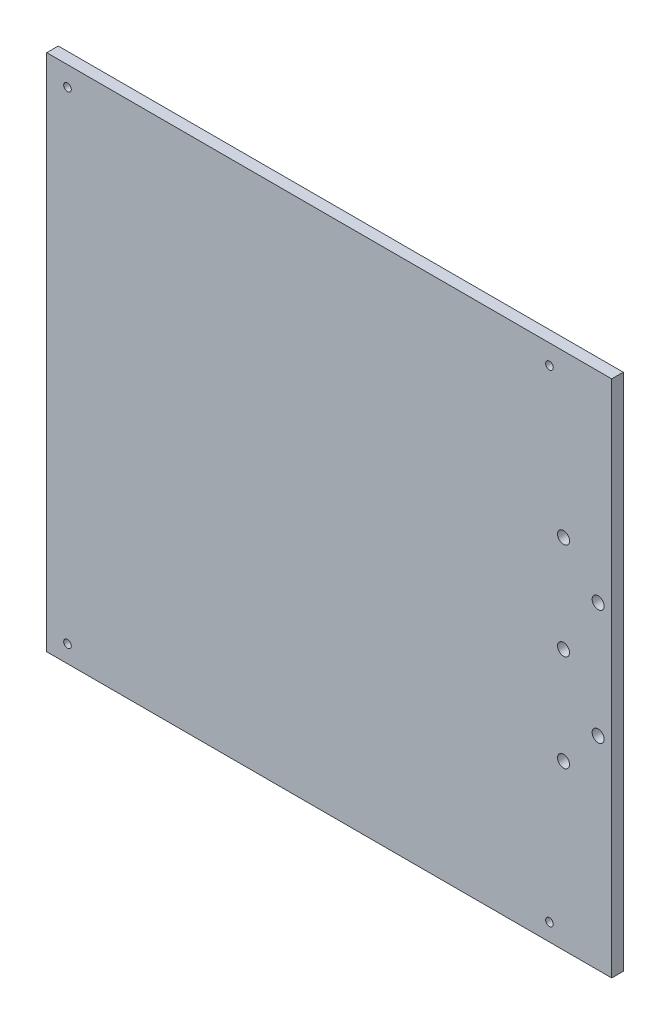
SolidWorks part; units mm, degrees
material "Lega 1060"
ref_plane "Piano frontale" through (0, 0, 0) normal (0, 0, 1) x (1, 0, 0)
ref_plane "Piano superiore" through (0, 0, 0) normal (0, 1, 0) x (1, 0, 0)
ref_plane "Piano destro" through (0, 0, 0) normal (1, 0, 0) x (0, 0, -1)
sketch "Schizzo1" plane through (0, 0, 0) normal (0, 0, 1) x (1, 0, 0)
  line L1 (0, 20) -> (-245, 20)
  line L2 (0, 20) -> (0, 245)
  line L3 (0, 245) -> (-245, 245)
  line L4 (-245, 20) -> (-245, 245)
  dimension "D1" = 245
  dimension "D2" = 225
  dimension "D3" = 20
extrude "Estrusione-Estrusione1" add sketch "Schizzo1" along normal blind 5
hole_wizard "Foro filettato M4-1" positions "Schizzo11" profile "Schizzo10" tap size "M4" standard "ISO" end condition up to next
sketch "Schizzo11" plane through (0, 0, 0) normal (0, 0, -1) x (-1, 0, 0)
  line L0 (245, 20) -> (0, 20) construction
  point P0 (236, 27.5)
  point P2 (27, 27.5)
  point P4 (236, 236.5)
  point P6 (27, 236.5)
  dimension "D1" = 7.5
  dimension "D2" = 209
  dimension "D3" = 209
  dimension "D4" = 9
sketch "Schizzo10" plane through (-236, 27.5, 0) normal (1, 0, 0) x (0, 1, 0)
  line L0 (0, 0) -> (0, 5)
  line L1 (0, 5) -> (1.65, 5)
  line L2 (1.65, 5) -> (1.65, 0)
  line L5 (1.65, 0) -> (0, 0)
  line L11 (0, -6.35) -> (0, 107.95) construction
  dimension "Thru Tap Drill Dia." = 3.3
  dimension "Thru Tap Drill Depth" = 5
cosmetic thread "Filettatura del foro2" parameters "D2"=4
cosmetic thread "Filettatura del foro4" parameters "D2"=4
cosmetic thread "Filettatura del foro5" parameters "D2"=4
cosmetic thread "Filettatura del foro6" parameters "D2"=4
sketch "Schizzo12" plane through (0, 0, 0) normal (0, 0, -1) x (-1, 0, 0)
  circle A0 centre (5.8957, 107.9884) radius 2.6
  circle A1 centre (5.8957, 157.9884) radius 2.6
  circle A2 centre (20.8957, 90.9884) radius 2.6
  circle A3 centre (20.8957, 132.9884) radius 2.6
  circle A4 centre (20.8957, 174.9884) radius 2.6
extrude "Taglio-Estrusione1" cut sketch "Schizzo12" against normal blind 10
